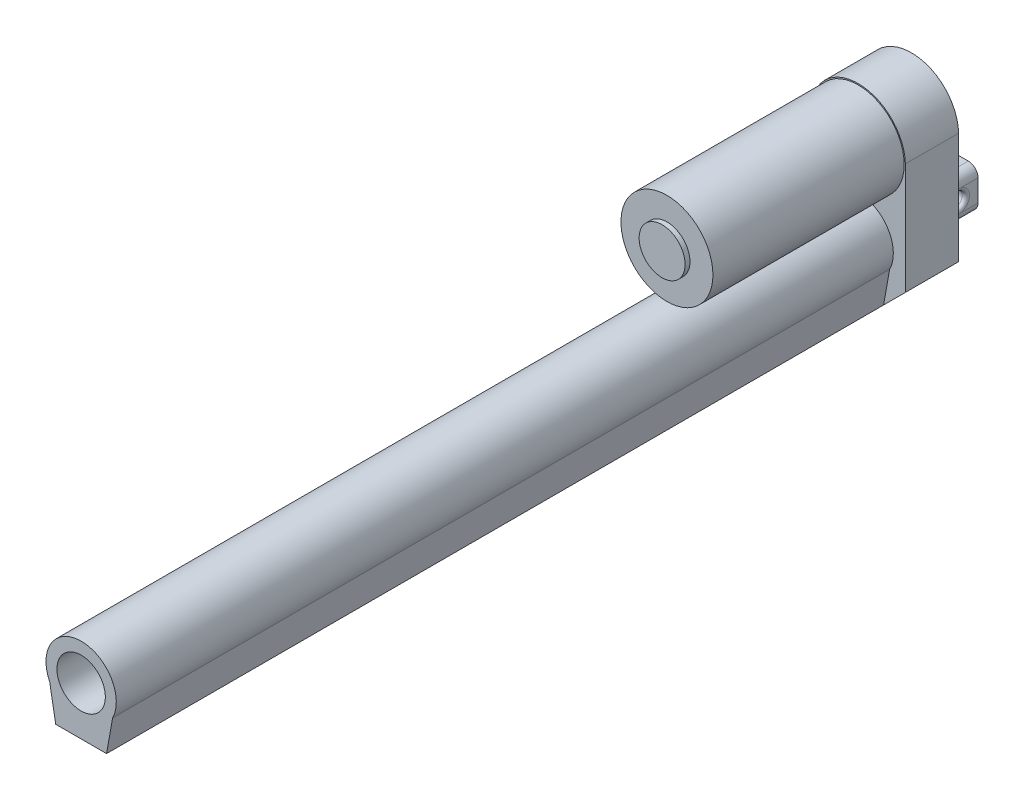
SolidWorks part; units mm, degrees
ref_plane "Alzado" through (0, 0, 0) normal (0, 0, 1) x (1, 0, 0)
ref_plane "Planta" through (0, 0, 0) normal (0, 1, 0) x (1, 0, 0)
ref_plane "Vista lateral" through (0, 0, 0) normal (1, 0, 0) x (0, 0, -1)
sketch "Croquis1" plane through (0, 0, 0) normal (0, 0, 1) x (1, 0, 0)
  line L0 (-19.5, 9) -> (-9, 9) construction
  line L1 (-9, 0) -> (-30, 0)
  line L2 (0, 9) -> (0, 54.9875)
  line L3 (-19.5, 74) -> (-39, 74) construction
  line L4 (-39, 9) -> (-39, 54.9875)
  line L5 (-19.5, 9) -> (-30, 9) construction
  line L6 (-30, 0) -> (-39, 9)
  line L7 (-19.5, 74) -> (-19.5, 0) construction
  line L8 (-30, 0) -> (-51.6279, 0) construction
  line L9 (-51.6279, 0) -> (-51.6279, 9) construction
  line L10 (-9, 0) -> (0, 9)
  line L12 (0, 74) -> (17.4492, 74) construction
  line L13 (17.4492, 74) -> (17.4492, 54) construction
  arc A0 (0, 54.9875) -> (-39, 54.9875) centre (-19.5, 54.4937) ccw
  dimension "D1" = 39
  dimension "D2" = 74
  dimension "D3" = 9
  dimension "D4" = 10.5
  dimension "D5" = 10.5
  dimension "D7" = 20
extrude "Saliente-Extruir1" add sketch "Croquis1" along normal blind 22
sketch "Croquis2" plane through (0, 0, 22) normal (0, 0, 1) x (1, 0, 0)
  line L0 (-19.5, 74) -> (-19.5, 73.5) construction
  line L1 (-19.5, 73.5) -> (-19.5, 54.5) construction
  arc A0 (0, 54.9875) -> (-39, 54.9875) centre (-19.5, 54.4937) ccw construction
  circle A1 centre (-19.5, 54.5) radius 19
  dimension "D1" = 0.5
  dimension "D2" = 19
extrude "Saliente-Extruir2" add sketch "Croquis2" along normal blind 79
sketch "Croquis3" plane through (0, 0, 101) normal (0, 0, 1) x (1, 0, 0)
  circle A0 centre (-19.5, 54.5) radius 9.5
extrude "Saliente-Extruir3" add sketch "Croquis3" along normal blind 2
sketch "Croquis4" plane through (0, 0, 22) normal (0, 0, 1) x (1, 0, 0)
  line L0 (-19.5, 0) -> (-19.5, 35) construction
  line L1 (-30, 0) -> (-9, 0) construction
  line L2 (-32.5, 0) -> (-32.5, 14) construction
  line L3 (-32.5, 14) -> (-19.5, 14) construction
  line L4 (-19.5, 14) -> (-6.5, 14) construction
  line L5 (-32.5, 14) -> (-30, 0)
  line L6 (-30, 0) -> (-9, 0)
  line L7 (-9, 0) -> (-6.5, 14)
  arc A0 (-32.5, 14) -> (-6.5, 14) centre (-19.5, 20.4772) cw
  dimension "D1" = 35
  dimension "D2" = 14
  dimension "D3" = 13
  dimension "D4" = 13
extrude "Saliente-Extruir4" add sketch "Croquis4" along normal blind 321
sketch "Croquis5" plane through (0, 0, 343) normal (0, 0, 1) x (1, 0, 0)
  line L0 (-19.5, 35.0014) -> (-19.5, 30.0014) construction
  line L1 (-19.5, 30.0014) -> (-19.5, 20.0014) construction
  arc A0 (-6.5, 14) -> (-32.5, 14) centre (-19.5, 20.4772) ccw construction
  circle A1 centre (-19.5, 20.0014) radius 10
  dimension "D1" = 5
  dimension "D2" = 10
extrude "Cortar-Extruir1" cut sketch "Croquis5" against normal up to surface (321 mm away) up to face at (-0.5, 54.5, 22)
sketch "Croquis6" plane through (0, 0, 0) normal (0, 0, -1) x (-1, 0, 0)
  line L0 (39, 31.9937) -> (28, 31.9937) construction
  line L1 (39, 54.9875) -> (39, 9) construction
  line L2 (19.5, 0) -> (19.5, 11) construction
  line L3 (30, 0) -> (9, 0) construction
  line L4 (24, 11) -> (19.5, 11)
  line L5 (28, 15) -> (28, 24)
  line L6 (24, 28) -> (15, 28)
  line L7 (11, 24) -> (11, 15)
  line L8 (15, 11) -> (19.5, 11)
  arc A0 (24, 11) -> (28, 15) centre (24, 15) ccw
  arc A1 (11, 15) -> (15, 11) centre (15, 15) ccw
  arc A2 (15, 28) -> (11, 24) centre (15, 24) ccw
  arc A3 (28, 24) -> (24, 28) centre (24, 24) ccw
  point P14 (28, 11)
  point P17 (11, 11)
  point P22 (28, 28)
  dimension "D5" = 4
  dimension "D1" = 11
  dimension "D2" = 11
  dimension "D3" = 17
  dimension "D4" = 8.5
extrude "Saliente-Extruir5" add sketch "Croquis6" along normal blind 19
sketch "Croquis8" plane through (-11, 0, 0) normal (1, 0, 0) x (0, 0, -1)
  line L0 (19, 19.5) -> (11, 19.5) construction
  line L1 (19, 24) -> (19, 15) construction
  circle A0 centre (11, 19.5) radius 3
  dimension "D2" = 6
  dimension "D1" = 8
extrude "Cortar-Extruir2" cut sketch "Croquis8" against normal up to next
fillet "Redondeo1" radius 1.5 2 edges at (-28, 22.5, -11) (-11, 22.5, -11)
sketch "Croquis9" plane through (0, 0, 343) normal (0, 0, 1) x (1, 0, 0)
  line L0 (-19.5, 35.0014) -> (-19.5, 0) construction
  line L1 (-30, 0) -> (-9, 0) construction
  line L2 (-4.9758, 20.4772) -> (-34.0242, 20.4772) construction
  line L3 (-6.5, 14) -> (-32.5, 14) construction
  arc A0 (-6.5, 14) -> (-32.5, 14) centre (-19.5, 20.4772) ccw construction
